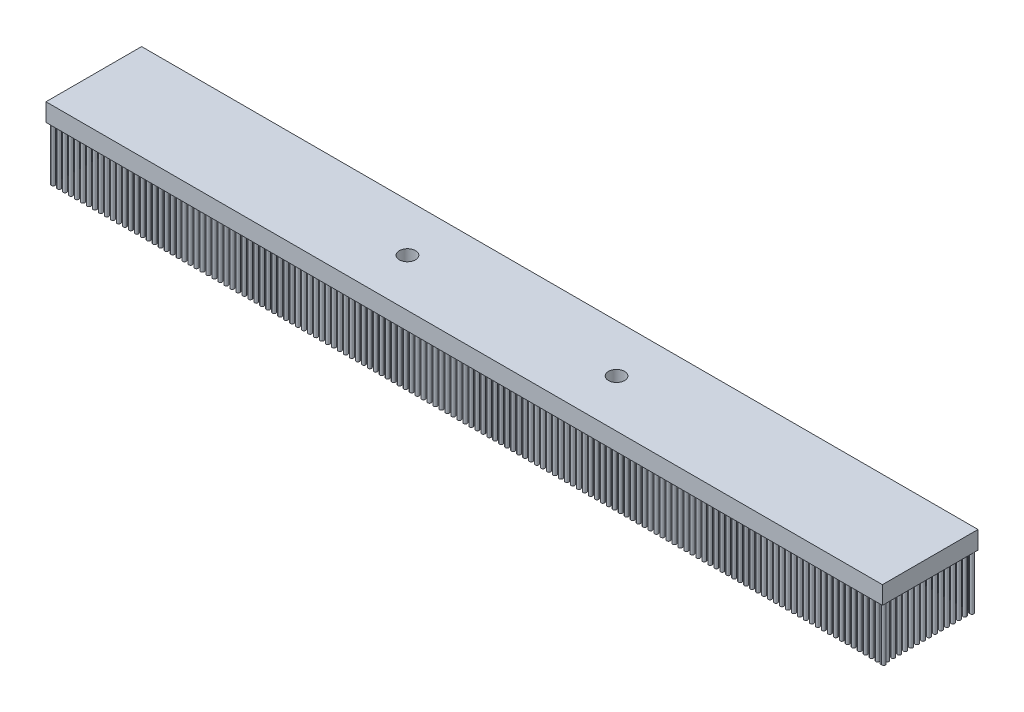
SolidWorks part; units mm, degrees
material "Maple"
ref_plane "Front Plane" through (0, 0, 0) normal (0, 0, 1) x (1, 0, 0)
ref_plane "Top Plane" through (0, 0, 0) normal (0, 1, 0) x (1, 0, 0)
ref_plane "Right Plane" through (0, 0, 0) normal (1, 0, 0) x (0, 0, -1)
sketch "Sketch1" plane through (0, 0, 0) normal (0, 1, 0) x (1, 0, 0)
  line L1 (-350, 40) -> (350, 40)
  line L2 (-350, 40) -> (-350, -40)
  line L3 (-350, -40) -> (350, -40)
  line L4 (350, 40) -> (350, -40)
  line L5 (-350, 40) -> (350, -40) construction
  line L6 (-350, -40) -> (350, 40) construction
  point P0 (0, 0)
  dimension "D1" = 700
  dimension "D2" = 80
extrude "Boss-Extrude1" add sketch "Sketch1" along normal blind 15
sketch "Sketch2" plane through (0, 0, 0) normal (0, 1, 0) x (1, 0, 0)
  line L0 (-8.25, 0) -> (8.25, 0) construction
  line L1 (0, -8.25) -> (0, 8.25) construction
  circle A0 centre (-347, 37) radius 1.5
  circle A1 centre (-342, 37) radius 1.5
  circle A2 centre (-337, 37) radius 1.5
  circle A3 centre (-332, 37) radius 1.5
  circle A4 centre (-327, 37) radius 1.5
  circle A5 centre (-322, 37) radius 1.5
  circle A6 centre (-317, 37) radius 1.5
  circle A7 centre (-312, 37) radius 1.5
  circle A8 centre (-307, 37) radius 1.5
  circle A9 centre (-302, 37) radius 1.5
  circle A10 centre (-297, 37) radius 1.5
  circle A11 centre (-292, 37) radius 1.5
  circle A12 centre (-287, 37) radius 1.5
  circle A13 centre (-282, 37) radius 1.5
  circle A14 centre (-277, 37) radius 1.5
  circle A15 centre (-272, 37) radius 1.5
  circle A16 centre (-267, 37) radius 1.5
  circle A17 centre (-262, 37) radius 1.5
  circle A18 centre (-257, 37) radius 1.5
  circle A19 centre (-252, 37) radius 1.5
  circle A20 centre (-247, 37) radius 1.5
  circle A21 centre (-242, 37) radius 1.5
  circle A22 centre (-237, 37) radius 1.5
  circle A23 centre (-232, 37) radius 1.5
  circle A24 centre (-227, 37) radius 1.5
  circle A25 centre (-222, 37) radius 1.5
  circle A26 centre (-217, 37) radius 1.5
  circle A27 centre (-212, 37) radius 1.5
  circle A28 centre (-207, 37) radius 1.5
  circle A29 centre (-202, 37) radius 1.5
  circle A30 centre (-197, 37) radius 1.5
  circle A31 centre (-192, 37) radius 1.5
  circle A32 centre (-187, 37) radius 1.5
  circle A33 centre (-182, 37) radius 1.5
  circle A34 centre (-177, 37) radius 1.5
  circle A35 centre (-172, 37) radius 1.5
  circle A36 centre (-167, 37) radius 1.5
  circle A37 centre (-162, 37) radius 1.5
  circle A38 centre (-157, 37) radius 1.5
  circle A39 centre (-152, 37) radius 1.5
  circle A40 centre (-147, 37) radius 1.5
  circle A41 centre (-142, 37) radius 1.5
  circle A42 centre (-137, 37) radius 1.5
  circle A43 centre (-132, 37) radius 1.5
  circle A44 centre (-127, 37) radius 1.5
  circle A45 centre (-122, 37) radius 1.5
  circle A46 centre (-117, 37) radius 1.5
  circle A47 centre (-112, 37) radius 1.5
  circle A48 centre (-107, 37) radius 1.5
  circle A49 centre (-102, 37) radius 1.5
  circle A50 centre (-97, 37) radius 1.5
  circle A51 centre (-92, 37) radius 1.5
  circle A52 centre (-87, 37) radius 1.5
  circle A53 centre (-82, 37) radius 1.5
  circle A54 centre (-77, 37) radius 1.5
  circle A55 centre (-72, 37) radius 1.5
  circle A56 centre (-67, 37) radius 1.5
  circle A57 centre (-62, 37) radius 1.5
  circle A58 centre (-57, 37) radius 1.5
  circle A59 centre (-52, 37) radius 1.5
  circle A60 centre (-47, 37) radius 1.5
  circle A61 centre (-42, 37) radius 1.5
  circle A62 centre (-37, 37) radius 1.5
  circle A63 centre (-32, 37) radius 1.5
  circle A64 centre (-27, 37) radius 1.5
  circle A65 centre (-22, 37) radius 1.5
  circle A66 centre (-17, 37) radius 1.5
  circle A67 centre (-12, 37) radius 1.5
  circle A68 centre (-7, 37) radius 1.5
  circle A69 centre (-2, 37) radius 1.5
  circle A70 centre (3, 37) radius 1.5
  circle A71 centre (8, 37) radius 1.5
  circle A72 centre (13, 37) radius 1.5
  circle A73 centre (18, 37) radius 1.5
  circle A74 centre (23, 37) radius 1.5
  circle A75 centre (28, 37) radius 1.5
  circle A76 centre (33, 37) radius 1.5
  circle A77 centre (38, 37) radius 1.5
  circle A78 centre (43, 37) radius 1.5
  circle A79 centre (48, 37) radius 1.5
  circle A80 centre (53, 37) radius 1.5
  circle A81 centre (58, 37) radius 1.5
  circle A82 centre (63, 37) radius 1.5
  circle A83 centre (68, 37) radius 1.5
  circle A84 centre (73, 37) radius 1.5
  circle A85 centre (78, 37) radius 1.5
  circle A86 centre (83, 37) radius 1.5
  circle A87 centre (88, 37) radius 1.5
  circle A88 centre (93, 37) radius 1.5
  circle A89 centre (98, 37) radius 1.5
  circle A90 centre (103, 37) radius 1.5
  circle A91 centre (108, 37) radius 1.5
  circle A92 centre (113, 37) radius 1.5
  circle A93 centre (118, 37) radius 1.5
  circle A94 centre (123, 37) radius 1.5
  circle A95 centre (128, 37) radius 1.5
  circle A96 centre (133, 37) radius 1.5
  circle A97 centre (138, 37) radius 1.5
  circle A98 centre (143, 37) radius 1.5
  circle A99 centre (148, 37) radius 1.5
  circle A100 centre (153, 37) radius 1.5
  circle A101 centre (158, 37) radius 1.5
  circle A102 centre (163, 37) radius 1.5
  circle A103 centre (168, 37) radius 1.5
  circle A104 centre (173, 37) radius 1.5
  circle A105 centre (178, 37) radius 1.5
  circle A106 centre (183, 37) radius 1.5
  circle A107 centre (188, 37) radius 1.5
  circle A108 centre (193, 37) radius 1.5
  circle A109 centre (198, 37) radius 1.5
  circle A110 centre (203, 37) radius 1.5
  circle A111 centre (208, 37) radius 1.5
  circle A112 centre (213, 37) radius 1.5
  circle A113 centre (218, 37) radius 1.5
  circle A114 centre (223, 37) radius 1.5
  circle A115 centre (228, 37) radius 1.5
  circle A116 centre (233, 37) radius 1.5
  circle A117 centre (238, 37) radius 1.5
  circle A118 centre (243, 37) radius 1.5
  circle A119 centre (248, 37) radius 1.5
  circle A120 centre (253, 37) radius 1.5
  circle A121 centre (258, 37) radius 1.5
  circle A122 centre (263, 37) radius 1.5
  circle A123 centre (268, 37) radius 1.5
  circle A124 centre (273, 37) radius 1.5
  circle A125 centre (278, 37) radius 1.5
  circle A126 centre (283, 37) radius 1.5
  circle A127 centre (288, 37) radius 1.5
  circle A128 centre (293, 37) radius 1.5
  circle A129 centre (298, 37) radius 1.5
  circle A130 centre (303, 37) radius 1.5
  circle A131 centre (308, 37) radius 1.5
  circle A132 centre (313, 37) radius 1.5
  circle A133 centre (318, 37) radius 1.5
  circle A134 centre (323, 37) radius 1.5
  circle A135 centre (328, 37) radius 1.5
  circle A136 centre (333, 37) radius 1.5
  circle A137 centre (338, 37) radius 1.5
  circle A138 centre (343, 37) radius 1.5
  circle A139 centre (348, 37) radius 1.5
  circle A140 centre (-347, 32) radius 1.5
  circle A141 centre (-347, 27) radius 1.5
  circle A142 centre (-347, 22) radius 1.5
  circle A143 centre (-347, 17) radius 1.5
  circle A144 centre (-347, 12) radius 1.5
  circle A145 centre (-347, 7) radius 1.5
  circle A146 centre (-347, 2) radius 1.5
  circle A147 centre (-347, -3) radius 1.5
  circle A148 centre (-347, -8) radius 1.5
  circle A149 centre (-347, -13) radius 1.5
  circle A150 centre (-347, -18) radius 1.5
  circle A151 centre (-347, -23) radius 1.5
  circle A152 centre (-347, -28) radius 1.5
  circle A153 centre (-347, -33) radius 1.5
  circle A154 centre (348, -37) radius 1.5
  circle A155 centre (343, -37) radius 1.5
  circle A156 centre (338, -37) radius 1.5
  circle A157 centre (333, -37) radius 1.5
  circle A158 centre (328, -37) radius 1.5
  circle A159 centre (323, -37) radius 1.5
  circle A160 centre (318, -37) radius 1.5
  circle A161 centre (313, -37) radius 1.5
  circle A162 centre (308, -37) radius 1.5
  circle A163 centre (303, -37) radius 1.5
  circle A164 centre (298, -37) radius 1.5
  circle A165 centre (293, -37) radius 1.5
  circle A166 centre (288, -37) radius 1.5
  circle A167 centre (283, -37) radius 1.5
  circle A168 centre (278, -37) radius 1.5
  circle A169 centre (273, -37) radius 1.5
  circle A170 centre (268, -37) radius 1.5
  circle A171 centre (263, -37) radius 1.5
  circle A172 centre (258, -37) radius 1.5
  circle A173 centre (253, -37) radius 1.5
  circle A174 centre (248, -37) radius 1.5
  circle A175 centre (243, -37) radius 1.5
  circle A176 centre (238, -37) radius 1.5
  circle A177 centre (233, -37) radius 1.5
  circle A178 centre (228, -37) radius 1.5
  circle A179 centre (223, -37) radius 1.5
  circle A180 centre (218, -37) radius 1.5
  circle A181 centre (213, -37) radius 1.5
  circle A182 centre (208, -37) radius 1.5
  circle A183 centre (203, -37) radius 1.5
  circle A184 centre (198, -37) radius 1.5
  circle A185 centre (193, -37) radius 1.5
  circle A186 centre (188, -37) radius 1.5
  circle A187 centre (183, -37) radius 1.5
  circle A188 centre (178, -37) radius 1.5
  circle A189 centre (173, -37) radius 1.5
  circle A190 centre (168, -37) radius 1.5
  circle A191 centre (163, -37) radius 1.5
  circle A192 centre (158, -37) radius 1.5
  circle A193 centre (153, -37) radius 1.5
  circle A194 centre (148, -37) radius 1.5
  circle A195 centre (143, -37) radius 1.5
  circle A196 centre (138, -37) radius 1.5
  circle A197 centre (133, -37) radius 1.5
  circle A198 centre (128, -37) radius 1.5
  circle A199 centre (123, -37) radius 1.5
  circle A200 centre (118, -37) radius 1.5
  circle A201 centre (113, -37) radius 1.5
  circle A202 centre (108, -37) radius 1.5
  circle A203 centre (103, -37) radius 1.5
  circle A204 centre (98, -37) radius 1.5
  circle A205 centre (93, -37) radius 1.5
  circle A206 centre (88, -37) radius 1.5
  circle A207 centre (83, -37) radius 1.5
  circle A208 centre (78, -37) radius 1.5
  circle A209 centre (73, -37) radius 1.5
  circle A210 centre (68, -37) radius 1.5
  circle A211 centre (63, -37) radius 1.5
  circle A212 centre (58, -37) radius 1.5
  circle A213 centre (53, -37) radius 1.5
  circle A214 centre (48, -37) radius 1.5
  circle A215 centre (43, -37) radius 1.5
  circle A216 centre (38, -37) radius 1.5
  circle A217 centre (33, -37) radius 1.5
  circle A218 centre (28, -37) radius 1.5
  circle A219 centre (23, -37) radius 1.5
  circle A220 centre (18, -37) radius 1.5
  circle A221 centre (13, -37) radius 1.5
  circle A222 centre (8, -37) radius 1.5
  circle A223 centre (3, -37) radius 1.5
  circle A224 centre (-2, -37) radius 1.5
  circle A225 centre (-7, -37) radius 1.5
  circle A226 centre (-12, -37) radius 1.5
  circle A227 centre (-17, -37) radius 1.5
  circle A228 centre (-22, -37) radius 1.5
  circle A229 centre (-27, -37) radius 1.5
  circle A230 centre (-32, -37) radius 1.5
  circle A231 centre (-37, -37) radius 1.5
  circle A232 centre (-42, -37) radius 1.5
  circle A233 centre (-47, -37) radius 1.5
  circle A234 centre (-52, -37) radius 1.5
  circle A235 centre (-57, -37) radius 1.5
  circle A236 centre (-62, -37) radius 1.5
  circle A237 centre (-67, -37) radius 1.5
  circle A238 centre (-72, -37) radius 1.5
  circle A239 centre (-77, -37) radius 1.5
  circle A240 centre (-82, -37) radius 1.5
  circle A241 centre (-87, -37) radius 1.5
  circle A242 centre (-92, -37) radius 1.5
  circle A243 centre (-97, -37) radius 1.5
  circle A244 centre (-102, -37) radius 1.5
  circle A245 centre (-107, -37) radius 1.5
  circle A246 centre (-112, -37) radius 1.5
  circle A247 centre (-117, -37) radius 1.5
  circle A248 centre (-122, -37) radius 1.5
  circle A249 centre (-127, -37) radius 1.5
  circle A250 centre (-132, -37) radius 1.5
  circle A251 centre (-137, -37) radius 1.5
  circle A252 centre (-142, -37) radius 1.5
  circle A253 centre (-147, -37) radius 1.5
  circle A254 centre (-152, -37) radius 1.5
  circle A255 centre (-157, -37) radius 1.5
  circle A256 centre (-162, -37) radius 1.5
  circle A257 centre (-167, -37) radius 1.5
  circle A258 centre (-172, -37) radius 1.5
  circle A259 centre (-177, -37) radius 1.5
  circle A260 centre (-182, -37) radius 1.5
  circle A261 centre (-187, -37) radius 1.5
  circle A262 centre (-192, -37) radius 1.5
  circle A263 centre (-197, -37) radius 1.5
  circle A264 centre (-202, -37) radius 1.5
  circle A265 centre (-207, -37) radius 1.5
  circle A266 centre (-212, -37) radius 1.5
  circle A267 centre (-217, -37) radius 1.5
  circle A268 centre (-222, -37) radius 1.5
  circle A269 centre (-227, -37) radius 1.5
  circle A270 centre (-232, -37) radius 1.5
  circle A271 centre (-237, -37) radius 1.5
  circle A272 centre (-242, -37) radius 1.5
  circle A273 centre (-247, -37) radius 1.5
  circle A274 centre (-252, -37) radius 1.5
  circle A275 centre (-257, -37) radius 1.5
  circle A276 centre (-262, -37) radius 1.5
  circle A277 centre (-267, -37) radius 1.5
  circle A278 centre (-272, -37) radius 1.5
  circle A279 centre (-277, -37) radius 1.5
  circle A280 centre (-282, -37) radius 1.5
  circle A281 centre (-287, -37) radius 1.5
  circle A282 centre (-292, -37) radius 1.5
  circle A283 centre (-297, -37) radius 1.5
  circle A284 centre (-302, -37) radius 1.5
  circle A285 centre (-307, -37) radius 1.5
  circle A286 centre (-312, -37) radius 1.5
  circle A287 centre (-317, -37) radius 1.5
  circle A288 centre (-322, -37) radius 1.5
  circle A289 centre (-327, -37) radius 1.5
  circle A290 centre (-332, -37) radius 1.5
  circle A291 centre (-337, -37) radius 1.5
  circle A292 centre (-342, -37) radius 1.5
  circle A293 centre (-347, -37) radius 1.5
  circle A294 centre (347, -37) radius 1.5
  circle A295 centre (347, -33) radius 1.5
  circle A296 centre (347, -28) radius 1.5
  circle A297 centre (347, -23) radius 1.5
  circle A298 centre (347, -18) radius 1.5
  circle A299 centre (347, -13) radius 1.5
  circle A300 centre (347, -8) radius 1.5
  circle A301 centre (347, -3) radius 1.5
  circle A302 centre (347, 2) radius 1.5
  circle A303 centre (347, 7) radius 1.5
  circle A304 centre (347, 12) radius 1.5
  circle A305 centre (347, 17) radius 1.5
  circle A306 centre (347, 22) radius 1.5
  circle A307 centre (347, 27) radius 1.5
  circle A308 centre (347, 32) radius 1.5
  circle A309 centre (347, 37) radius 1.5
  dimension "D1" = 3
  dimension "D2" = 347
  dimension "D3" = 37
  dimension "D4" = 140
  dimension "D5" = 15
extrude "Boss-Extrude2" add sketch "Sketch2" against normal blind 45
sketch "Sketch3" plane through (0, 0, 0) normal (0, 1, 0) x (1, 0, 0)
  line L0 (-87.5, 0) -> (87.5, 0) construction
  circle A0 centre (-87.5, 0) radius 6.725
  circle A1 centre (87.5, 0) radius 6.725
  point P4 (0, 0)
  dimension "D2" = 13.45
  dimension "D1" = 175
extrude "Cut-Extrude1" cut sketch "Sketch3" against normal through all both and the other way through all
equation "\"broomLength\"= 700mm"
equation "\"broomWidth\"= 80mm"
equation "\"D1@Sketch1\"=\"broomLength\""
equation "\"D2@Sketch1\"=\"broomWidth\""
equation "\"D2@Sketch2\"=\"broomLength\"/2 -3"
equation "\"D3@Sketch2\"=\"broomWidth\"/2 - 3"
equation "\"mountHoleDiameter\"= 1in / 2 + 0.75"
equation "\"D2@Sketch3\"=\"mountHoleDiameter\""
